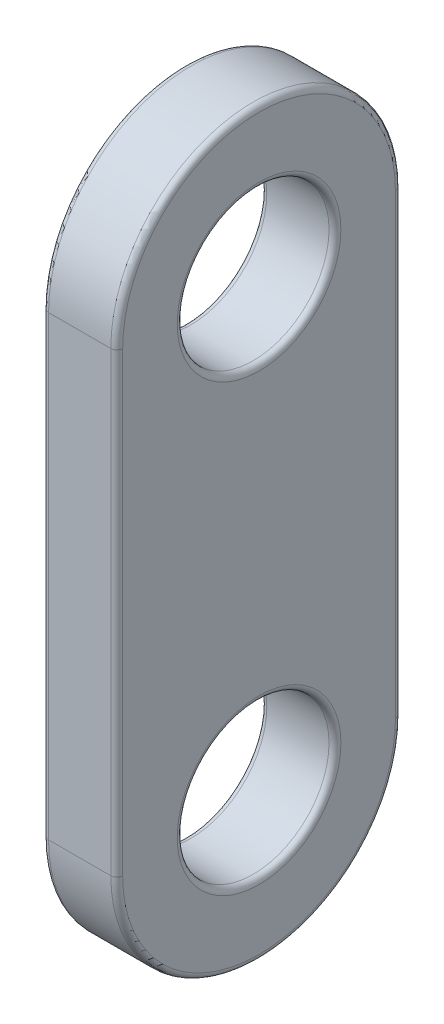
SolidWorks part; units mm, degrees
material "ABS"
ref_plane "Front Plane" through (0, 0, 0) normal (0, 0, 1) x (1, 0, 0)
ref_plane "Top Plane" through (0, 0, 0) normal (0, 1, 0) x (1, 0, 0)
ref_plane "Right Plane" through (0, 0, 0) normal (1, 0, 0) x (0, 0, -1)
sketch "Sketch1" plane through (0, 0, 0) normal (1, 0, 0) x (0, 0, -1)
  line L0 (0, 9.525) -> (0, -9.525) construction
  line L2 (-6.096, 15.875) -> (6.096, 15.875)
  line L3 (-6.096, 15.875) -> (-6.096, -15.875)
  line L4 (-6.096, -15.875) -> (6.096, -15.875)
  line L5 (6.096, 15.875) -> (6.096, -15.875)
  line L6 (-6.096, 15.875) -> (6.096, -15.875) construction
  line L7 (-6.096, -15.875) -> (6.096, 15.875) construction
  circle A0 centre (0, 9.525) radius 3.2512
  circle A1 centre (0, -9.525) radius 3.2512
  point P5 (0, 0)
  dimension "D2" = 6.5024
  dimension "D1" = 19.05
  dimension "D3" = 31.75
  dimension "D4" = 12.192
extrude "Boss-Extrude1" add sketch "Sketch1" along normal mid plane 3.175
fillet "Fillet1" 2 edges at (0, 15.875, 6.096) (0, 15.875, -6.096) type full round first side face at (0, 0, 6.096) second side face at (0, 0, -6.096) middle face at (0, 15.875, 0)
fillet "Fillet2" 2 edges at (0, -15.875, 6.096) (0, -15.875, -6.096) type full round first side face at (0, -3.048, 6.096) second side face at (0, -3.048, -6.096) middle face at (0, -15.875, 0)
fillet "Fillet3" radius 0.254 12 edges at (-1.5875, -9.525, -3.2512) (1.5875, -9.525, -3.2512) (-1.5875, 9.525, -3.2512) (1.5875, 9.525, -3.2512) (-1.5875, 0, -6.096) (-1.5875, 0, 6.096) (1.5875, 0, -6.096) (1.5875, 15.875, 0) (-1.5875, 15.875, 0) (-1.5875, -15.875, 0) (1.5875, -15.875, 0) (1.5875, 0, 6.096)
